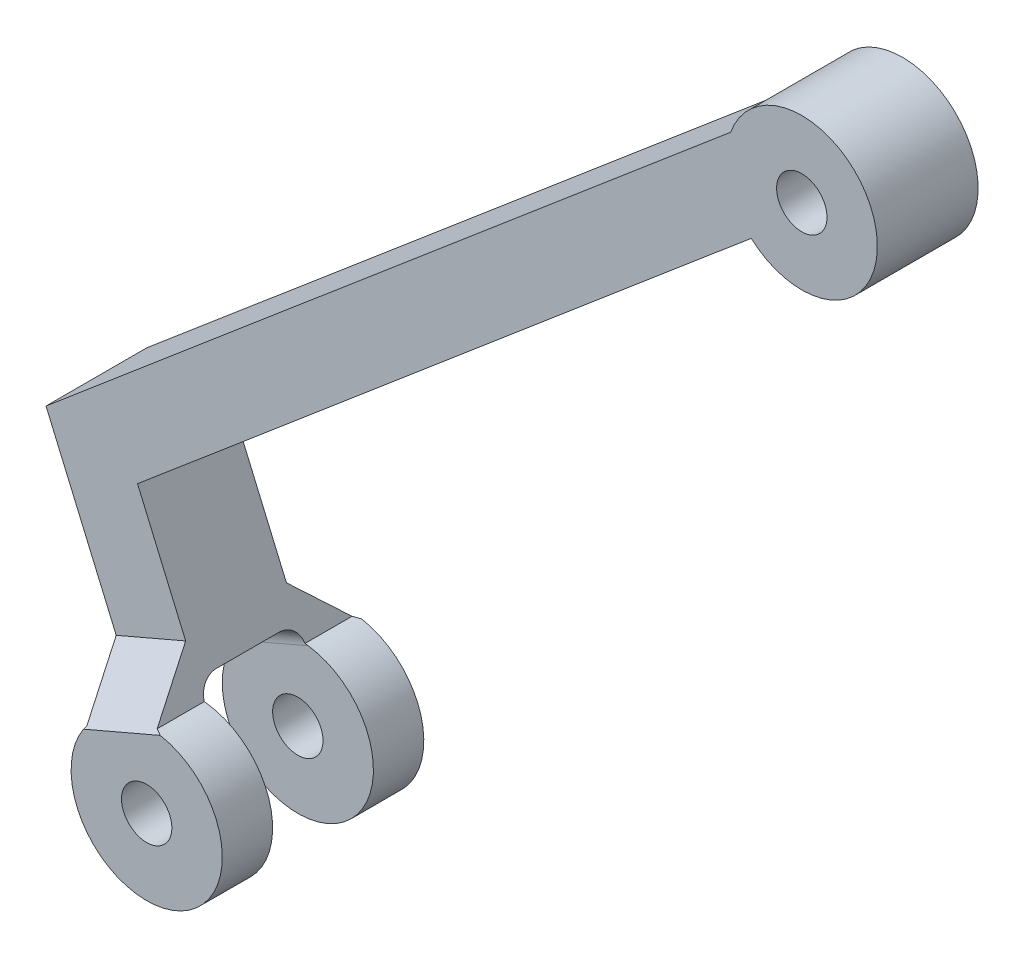
SolidWorks part; units mm, degrees
ref_plane "Спереди" through (0, 0, 0) normal (0, 0, 1) x (1, 0, 0)
ref_plane "Сверху" through (0, 0, 0) normal (0, 1, 0) x (1, 0, 0)
ref_plane "Справа" through (0, 0, 0) normal (1, 0, 0) x (0, 0, -1)
sketch "Sketch5" plane through (0, 0, 0) normal (0, 0, 1) x (1, 0, 0)
  line L0 (1.7523, 0.4742) -> (37.3029, 86.8114) construction
  line L1 (-1.0106, -0.6044) -> (29.6618, 87.5839) construction
  line L2 (0, 0) -> (17.8901, 43.1295)
  line L3 (0, 0) -> (114.3643, 0) construction
  line L4 (23.8823, 39.6684) -> (24.5035, 51.2503)
  line B0 (17.4507, 115.16) -> (29.9551, 112.6983)
  spline B1 degree 3 poles (29.9551, 112.6983) (28.321, 116.0983) (27.9284, 121.1676) (30.1713, 134.4746) (29.8473, 132.0116) (30.6222, 139.9349) (27.0176, 140.9027) knots 0 0 0 0 0.297085 0.369784 0.687298 1 1 1 1
  spline B2 degree 2 poles (27.0176, 140.9027) (20.5603, 128.6427) (17.4507, 115.16) knots 0 0 0 1 1 1
  spline B3 degree 2 poles (27.0176, 140.9027) (26.5004, 134.6878) (22.2537, 130.5645) knots 0 0 0 1 1 1
  line B4 (17.1977, 114.3508) -> (29.842, 112.2111)
  line B5 (28.7001, 84.8969) -> (10.3668, 87.513)
  spline B6 degree 1 poles (17.1977, 114.3508) (10.3668, 87.513) knots 0 0 1 1
  spline B7 degree 2 poles (29.842, 112.2111) (22.5534, 98.8452) (28.7001, 84.8969) knots 0 0 0 1 1 1
  line B8 (10.1904, 87.4159) -> (28.2572, 84.4958)
  line B9 (32.8909, 45.7292) -> (10.0695, 42.8593)
  spline B10 degree 2 poles (10.1904, 87.4159) (10.0234, 65.1379) (10.0695, 42.8593) knots 0 0 0 1 1 1
  spline B11 degree 2 poles (28.2572, 84.4958) (20.6417, 64.1094) (32.8909, 45.7292) knots 0 0 0 1 1 1
  line B12 (10.2797, 36.8758) -> (3.9253, -13.9853)
  line B13 (3.9253, -13.9853) -> (33.9594, -31.0804)
  line B14 (33.9594, -31.0804) -> (45.9193, -27.7969)
  line B15 (45.9193, -27.7969) -> (58.2918, -13.9853)
  line B16 (58.2918, -13.9853) -> (69.0331, -4.9875)
  line B17 (69.0331, -4.9875) -> (82.514, 2.0236)
  line B18 (82.514, 2.0236) -> (89.2736, 3.8794)
  line B19 (89.2736, 3.8794) -> (92.4846, 9.5208)
  line B20 (92.4846, 9.5208) -> (96.8914, 17.263)
  line B21 (96.8914, 17.263) -> (101.4978, 21.1217)
  line B22 (101.4978, 21.1217) -> (103.9241, 23.1541)
  line B23 (104.261, 27.4157) -> (104.5375, 25.5318)
  line B24 (84.192, 21.2056) -> (87.7484, 22.7822)
  line B25 (87.7484, 22.7822) -> (92.912, 27.4956)
  line B26 (71.6086, 15.6268) -> (84.192, 21.2056)
  line B27 (92.912, 27.4956) -> (95.357, 29.7274)
  line B28 (95.357, 29.7274) -> (96.8049, 29.9399)
  line B29 (71.6086, 15.6268) -> (53.4239, 15.2713)
  line B30 (48.0904, 17.5622) -> (39.9394, 26.4919)
  line B31 (39.9394, 26.4919) -> (33.9594, 37.99)
  line B32 (33.9594, 37.99) -> (10.2797, 36.8758)
  line B33 (96.8049, 29.9399) -> (99.4078, 30.2175)
  line B34 (99.4078, 30.2175) -> (102.2786, 29.261)
  line B35 (102.2786, 29.261) -> (104.261, 27.4157)
  line B36 (104.5375, 25.5318) -> (103.9241, 23.1541)
  arc B37 (53.4239, 15.2713) -> (48.0904, 17.5622) centre (53.2864, 22.3051) cw
  spline B38 degree 3 poles (104.261, 27.4157) (103.5289, 27.0494) (99.8378, 26.2685) (94.8982, 17.2338) (98.6516, 18.7375) knots 0 0 0 0 0.441207 1 1 1 1
  line B39 (27.7375, 116.5129) -> (14.1959, 87.8955)
  line B40 (27.7375, 116.5129) -> (25.9485, 114.8372)
  line B41 (25.9485, 114.8372) -> (27.5763, 114.067)
  line B42 (27.7375, 116.5129) -> (27.5763, 114.067)
  line B43 (26.1527, 88.0864) -> (17.8901, 43.1295)
  line B44 (19.3622, 85.005) -> (23.8823, 39.6684)
  line B45 (19.3622, 85.005) -> (17.7584, 73.9508)
  line B46 (17.7584, 73.9508) -> (23.117, 74.485)
  line B47 (23.117, 74.485) -> (19.3622, 85.005)
  line B48 (26.1527, 88.0864) -> (23.7481, 82.7635)
  line B49 (23.7481, 82.7635) -> (25.1278, 82.5099)
  line B50 (25.1278, 82.5099) -> (26.5087, 82.2561)
  line B51 (26.5087, 82.2561) -> (26.1527, 88.0864)
  line B52 (26.1527, 88.0864) -> (19.3622, 85.005)
  line B53 (19.3622, 85.005) -> (22.3683, 87.7853)
  line B54 (22.3683, 87.7853) -> (22.9012, 86.6109)
  line B55 (22.9012, 86.6109) -> (23.4998, 85.2917)
  line B56 (23.4998, 85.2917) -> (19.3622, 85.005)
  dimension "D1" = 93.37
  dimension "D2" = 93.37
  dimension "D4" = 67.471
  dimension "D5" = 8.764
sketch_block_instance "Block1-1"
sketch_block "Block1"
sketch_block_instance "Block2-1"
sketch_block "Block2"
sketch_block_instance "Block3-1"
sketch_block "Block3"
sketch_block_instance "Block18-1"
sketch_block "Block18"
sketch_block_instance "Block44-1"
sketch_block "Block44"
sketch_block_instance "Block46-1"
sketch_block "Block46"
sketch_block_instance "Block47-1"
sketch_block "Block47"
sketch_block_instance "Block48-1"
sketch_block "Block48"
sketch_block_instance "Block50-1"
sketch_block "Block50"
sketch "Sketch7" plane through (0, 0, 0) normal (0, 0, 1) x (1, 0, 0)
  line L0 (15.4454, 44.8683) -> (11.8939, 53.1379)
  line L1 (11.8939, 53.1379) -> (39.0692, 76.135)
  line L2 (39.8869, 72.8969) -> (15.5264, 52.2819)
  line L3 (15.5264, 52.2819) -> (18.1745, 46.116)
  circle A0 centre (17.8901, 43.1295) radius 3
  circle A1 centre (41.8945, 75.1262) radius 3
  circle A2 centre (17.8901, 43.1295) radius 1
  circle A3 centre (41.8945, 75.1262) radius 1
  point P8 (0, 0)
  point P13 (0, 0)
  point P14 (0, 0)
  point P15 (0, 0)
  point P16 (0, 0)
  point P17 (0, 0)
  point P18 (0, 0)
  point P19 (0, 0)
  point P20 (0, 0)
  point P21 (16.8816, 45.9549)
  point P22 (0, 0)
  point P23 (0, 0)
  point P24 (0, 0)
  point P25 (0, 0)
  point P26 (0, 0)
  point P27 (0, 0)
  point P28 (15.4394, 44.8598)
  point P29 (0, 0)
  point P30 (11.6267, 53.7601)
  point P31 (0, 0)
  dimension "D1" = 2
  dimension "D2" = 6
  dimension "D3" = 6
  dimension "D4" = 3
  dimension "D5" = 3
  dimension "D6" = 40
  dimension "D7" = 9
extrude "Boss-Extrude1" add sketch "Sketch7" along normal mid plane 4 contours A1 L1 L0 A0 L3 L2 | A0 A2 | A1 A3 region at (24.3353, 60.8617, 0) region at (16.678, 45.7807, 0) region at (42.3919, 77.9986, 0)
sketch "Sketch9" plane through (0, 0, 0) normal (0, 0, 1) x (1, 0, 0)
  line L0 (15.5264, 52.2819) -> (18.1745, 46.116) construction
  line L1 (15.4454, 44.8683) -> (11.8939, 53.1379) construction
  line L2 (17.4373, 47.8325) -> (18.1745, 46.116)
  line L3 (15.4454, 44.8683) -> (14.6808, 46.6487)
  line L4 (14.6808, 46.6487) -> (17.4373, 47.8325)
  arc A0 (15.4454, 44.8683) -> (18.1745, 46.116) centre (17.8901, 43.1295) ccw construction
  arc A1 (15.4454, 44.8683) -> (18.1745, 46.116) centre (17.8901, 43.1295) ccw
  circle A2 centre (17.8901, 43.1295) radius 1
  dimension "D1" = 4.5
extrude "Boss-Extrude2" add sketch "Sketch9" along normal mid plane 8
sketch "Sketch10" plane through (32.0655, 13.7709, 0) normal (0.9188, 0.3946, 0) x (0, 0, -1)
  line L0 (-4, 35.2018) -> (-4, 37.0699) construction
  line L1 (2, 27.3858) -> (-2, 27.3858)
  line L2 (2, 27.3858) -> (2, 35.8858)
  line L3 (2, 35.8858) -> (-2, 35.8858)
  line L4 (-2, 27.3858) -> (-2, 35.8858)
  line L6 (-4, 35.2018) -> (-4, 29.5699) construction
  point P0 (0, 32.3858)
  point P5 (0, 0)
  point P13 (-4, 32.3858)
  dimension "D1" = 4
  dimension "D2" = 2
  dimension "D3" = 3.5
  dimension "D4" = 5
  dimension "D5" = 4
extrude "Cut-Extrude3" cut sketch "Sketch10" against normal through all both and the other way through all
chamfer "Chamfer1" distance 2 angle 45 2 edges at (16.059, 47.2406, -4) (16.059, 47.2406, 4)
fillet "Fillet10" radius 0.75 2 edges at (16.5263, 46.1526, -2) (16.5263, 46.1526, 2)
